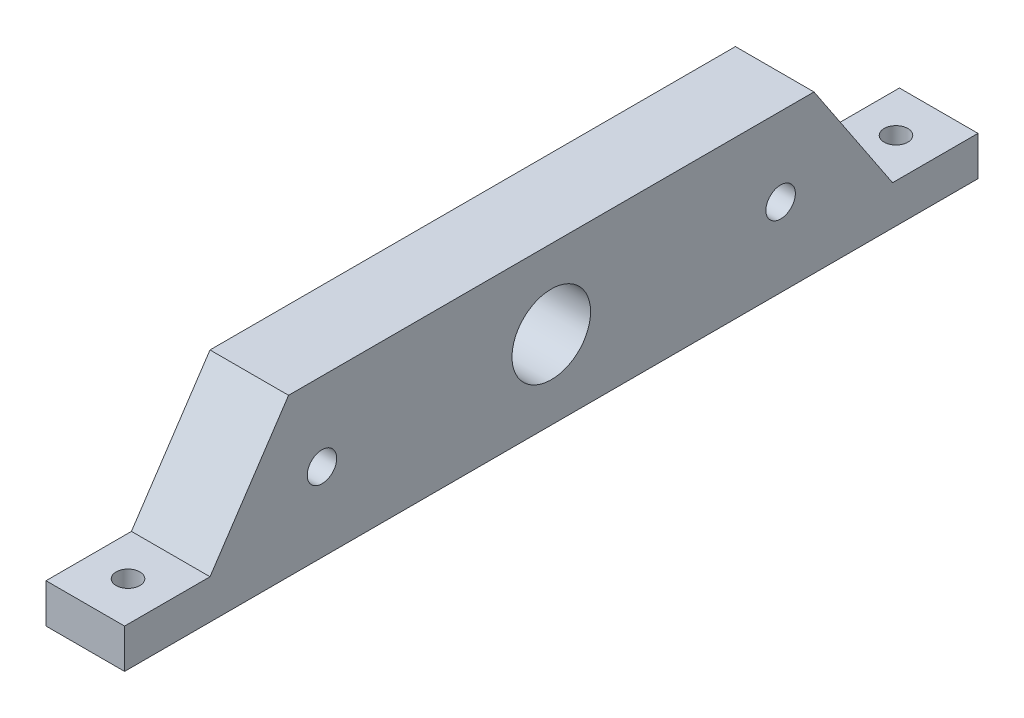
SolidWorks part; units mm, degrees
ref_plane "Front Plane" through (0, 0, 0) normal (0, 0, 1) x (1, 0, 0)
ref_plane "Top Plane" through (0, 0, 0) normal (0, 1, 0) x (1, 0, 0)
ref_plane "Right Plane" through (0, 0, 0) normal (1, 0, 0) x (0, 0, -1)
sketch "Sketch2" plane through (0, 0, 0) normal (1, 0, 0) x (0, 0, -1)
  line L1 (0, 0) -> (380, 0)
  line L2 (0, 0) -> (0, 40)
  line L3 (0, 40) -> (380, 40)
  line L4 (380, 0) -> (380, 40)
  line L5 (190, 0) -> (275.0005, 0)
  circle A2 centre (190, 20) radius 10
  circle A3 centre (131.63, 20) radius 3.75
  circle A4 centre (248.37, 20) radius 3.75
  dimension "D1" = 20
extrude "Boss-Extrude2" add sketch "Sketch2" along normal blind 20 contours L1 L4 L3 L2 A2 region at (0, 20, -3.821)
sketch "Sketch3" plane through (0, 0, 0) normal (-1, 0, 0) x (0, 0, 1)
  line L0 (-190, 20) -> (-131.635, 20)
  line L1 (-190, 20) -> (-248.365, 20)
  dimension "D1" = 58.365
  dimension "D2" = 58.365
sketch "Sketch4" plane through (20, 0, 0) normal (1, 0, 0) x (0, 0, -1)
  line L1 (0, 0) -> (380, 0) construction
  line L3 (0, 40) -> (380, 40) construction
  line L4 (123.1292, 40) -> (0, 40)
  line L5 (0, 40) -> (0, 0)
  line L7 (103.136, 10) -> (123.1292, 40)
  line L12 (103.136, 10) -> (81.389, 10)
  line L13 (81.389, 10) -> (81.389, 0)
  line L14 (81.389, 0) -> (0, 0)
  line L16 (298.611, 10) -> (298.611, 0)
  line L17 (276.864, 10) -> (298.611, 10)
  line L18 (276.864, 10) -> (256.8708, 40)
  line L19 (256.8708, 40) -> (380, 40)
  line L20 (380, 40) -> (380, 0)
  line L21 (298.611, 0) -> (380, 0)
  line M9 (0, 0) -> (380, 0)
  line M10 (380, 0) -> (380, 40)
  line M11 (380, 40) -> (0, 40)
  line M12 (0, 40) -> (0, 0)
extrude "Cut-Extrude1" cut sketch "Sketch4" against normal blind 100 contours M9 M11 M12 | M9 M10 M11 region at (20, 21.4879, -53.6151) region at (20, 21.4879, -326.3849)
sketch "Sketch5" plane through (0, 10, 0) normal (0, 1, 0) x (1, 0, 0)
  circle A0 centre (10, 92.2625) radius 3.0234
  circle A1 centre (10, 287.7375) radius 3.0234
extrude "Cut-Extrude2" cut sketch "Sketch5" against normal through all both and the other way through all
